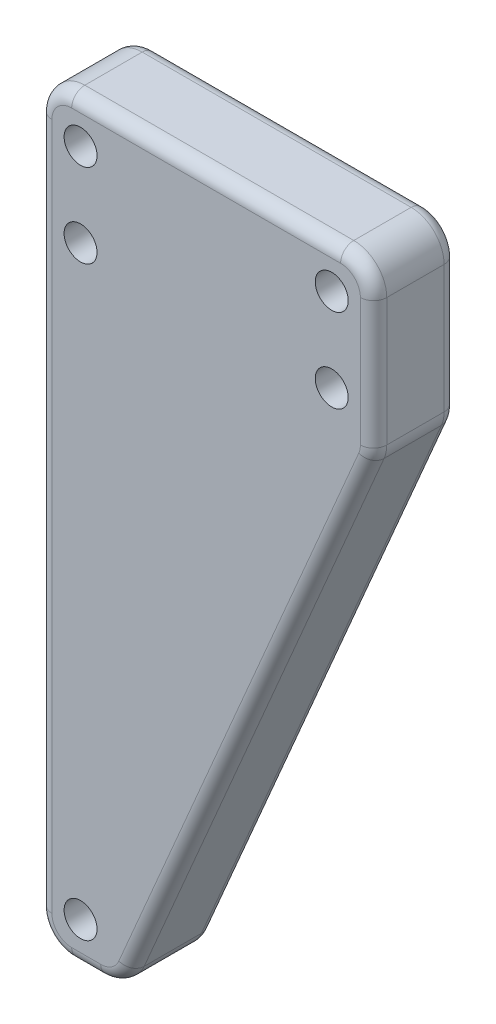
SolidWorks part; units mm, degrees
ref_plane "Front Plane" through (0, 0, 0) normal (0, 0, 1) x (1, 0, 0)
ref_plane "Top Plane" through (0, 0, 0) normal (0, 1, 0) x (1, 0, 0)
ref_plane "Right Plane" through (0, 0, 0) normal (1, 0, 0) x (0, 0, -1)
sketch "Sketch1" plane through (0, 0, 0) normal (0, 0, 1) x (1, 0, 0)
  line L0 (0, 0) -> (0, -114.3)
  line L1 (0, -114.3) -> (12.7, -114.3)
  line L2 (12.7, -114.3) -> (50.8, -25.4)
  line L3 (50.8, -25.4) -> (50.8, 0)
  line L4 (50.8, 0) -> (0, 0)
  circle A0 centre (6.35, -6.35) radius 2.5
  circle A1 centre (6.35, -107.95) radius 2.5
  circle A2 centre (44.45, -6.35) radius 2.5
  circle A3 centre (44.45, -19.05) radius 2.5
  circle A4 centre (6.35, -19.05) radius 2.5
  dimension "D7" = 5
  dimension "D1" = 114.3
  dimension "D2" = 50.8
  dimension "D3" = 25.4
  dimension "D4" = 12.7
  dimension "D5" = 6.35
  dimension "D6" = 6.35
  dimension "D8" = 6.35
  dimension "D9" = 2
  dimension "D10" = 2
extrude "Boss-Extrude1" add sketch "Sketch1" along normal blind 12.7
sketch "Sketch2" plane through (0, 0, 12.7) normal (0, 0, 1) x (1, 0, 0)
  line L1 (6.35, -113.0018) -> (10.725, -110.4759)
  line L2 (10.725, -110.4759) -> (10.725, -105.4241)
  line L3 (10.725, -105.4241) -> (6.35, -102.8982)
  line L4 (6.35, -102.8982) -> (1.975, -105.4241)
  line L5 (1.975, -105.4241) -> (1.975, -110.4759)
  line L6 (1.975, -110.4759) -> (6.35, -113.0018)
  circle A0 centre (6.35, -107.95) radius 4.375 construction
  point P0 (6.35, -107.95)
  dimension "D1" = 8.75
extrude "Cut-Extrude1" cut sketch "Sketch2" along normal blind 4.5 from surface starting at face at (22.86, -50.8, 0)
fillet "Fillet1" radius 5 5 edges at (0, -114.3, 6.35) (12.7, -114.3, 6.35) (50.8, -25.4, 6.35) (50.8, 0, 6.35) (0, 0, 6.35)
fillet "Fillet2" radius 2 20 edges at (50.6979, -25.379, 12.7) (32.1972, -68.8065, 12.7) (12.1555, -113.4742, 12.7) (7.2015, -114.3, 12.7) (1.4645, -112.8355, 12.7) (0, -57.15, 12.7) (1.4645, -1.4645, 12.7) (25.4, 0, 12.7) (49.3355, -1.4645, 12.7) (12.1555, -113.4742, 0) (7.2015, -114.3, 0) (1.4645, -112.8355, 0) (0, -57.15, 0) (1.4645, -1.4645, 0) (25.4, 0, 0) (49.3355, -1.4645, 0) (50.8, -14.6869, 0) (50.6979, -25.379, 0) (50.8, -14.6869, 12.7) (32.1972, -68.8065, 0)
